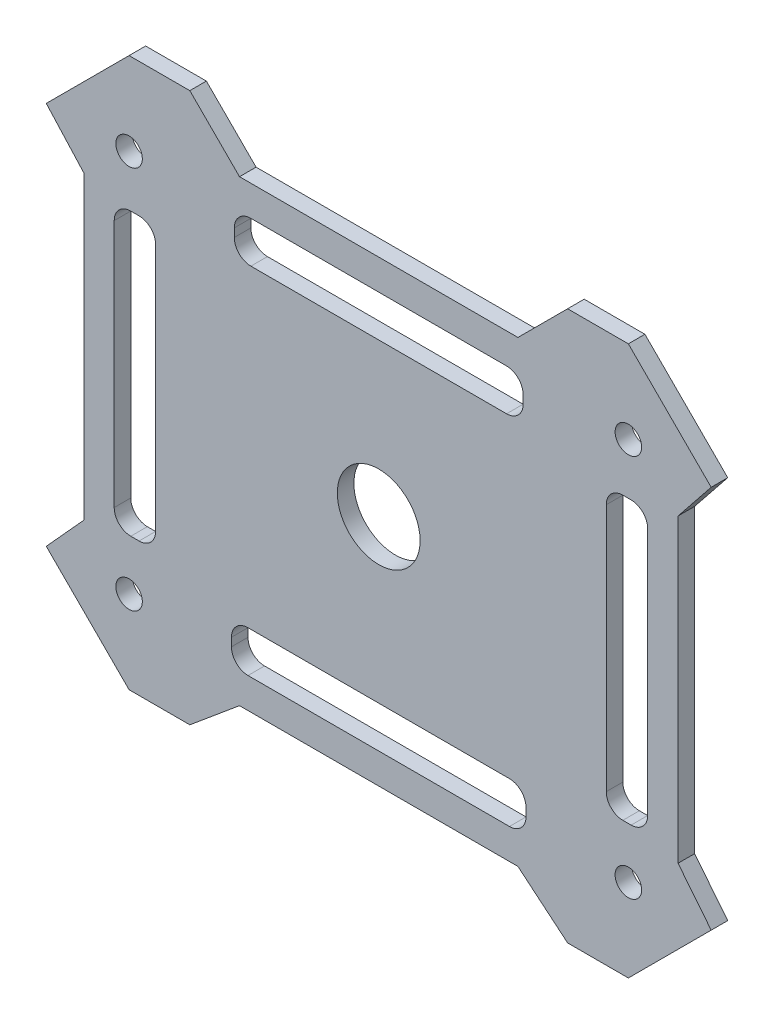
SolidWorks part; units mm, degrees
ref_plane "Front Plane" through (0, 0, 0) normal (0, 0, 1) x (1, 0, 0)
ref_plane "Top Plane" through (0, 0, 0) normal (0, 1, 0) x (1, 0, 0)
ref_plane "Right Plane" through (0, 0, 0) normal (1, 0, 0) x (0, 0, -1)
sketch "Sketch1" plane through (0, 0, 0) normal (0, 0, 1) x (1, 0, 0)
  line L0 (-66.8215, 56.7885) -> (-51.8215, 71.7885)
  line L1 (-31.8215, 62.7885) -> (18.6025, 62.7885)
  line L2 (47.6025, 49.2885) -> (47.6025, -5.1805)
  line L3 (-66.8215, -12.6805) -> (-60.0143, -5.1805)
  line L4 (-40.8215, 71.7885) -> (-31.8215, 62.7885)
  line L5 (-51.8215, 71.7885) -> (-40.8215, 71.7885)
  line L6 (38.6025, 71.7885) -> (53.6025, 56.7885)
  line L7 (-66.8215, -12.6805) -> (-51.8215, -27.6805)
  line L8 (-51.8215, -27.6805) -> (-40.8215, -27.6805)
  line L9 (38.6025, -27.6805) -> (53.6025, -12.6805)
  line L10 (27.6025, -27.6805) -> (38.6025, -27.6805)
  line L11 (27.6025, 71.7885) -> (38.6025, 71.7885)
  line L12 (-60.0143, 49.2885) -> (-66.8215, 56.7885)
  line L14 (18.6025, -20.1805) -> (-31.8215, -20.1805)
  line L15 (47.6025, 49.2885) -> (53.6025, 56.7885)
  line L16 (47.6025, -5.1805) -> (53.6025, -12.6805)
  line L17 (18.6025, 62.7885) -> (27.6025, 71.7885)
  line L18 (-31.8215, -20.1805) -> (-40.8215, -27.6805)
  line L19 (18.6025, -20.1805) -> (27.6025, -27.6805)
  line L20 (-51.5143, 47.554) -> (-50.0143, 47.554)
  line L21 (-54.5143, 44.554) -> (-54.5143, -0.446)
  line L22 (-51.5143, -3.446) -> (-50.0143, -3.446)
  line L23 (-47.0143, 44.554) -> (-47.0143, -0.446)
  line L24 (-29.7649, 57.2885) -> (16.546, 57.2885)
  line L25 (-32.7649, 54.2885) -> (-32.7649, 52.7885)
  line L26 (-29.7649, 49.7885) -> (16.546, 49.7885)
  line L27 (19.546, 54.2885) -> (19.546, 52.7885)
  line L28 (39.1025, 47.554) -> (37.6025, 47.554)
  line L29 (42.1025, 44.554) -> (42.1025, -0.446)
  line L30 (39.1025, -3.446) -> (37.6025, -3.446)
  line L31 (34.6025, 44.554) -> (34.6025, -0.446)
  line L32 (17.068, -14.6805) -> (-30.287, -14.6805)
  line L33 (20.068, -11.6805) -> (20.068, -10.1805)
  line L34 (17.068, -7.1805) -> (-30.287, -7.1805)
  line L35 (-33.287, -11.6805) -> (-33.287, -10.1805)
  line L36 (-60.0143, 49.2885) -> (-60.0143, -5.1805)
  arc A0 (39.1025, -3.446) -> (42.1025, -0.446) centre (39.1025, -0.446) ccw
  arc A1 (34.6025, -0.446) -> (37.6025, -3.446) centre (37.6025, -0.446) ccw
  arc A2 (42.1025, 44.554) -> (39.1025, 47.554) centre (39.1025, 44.554) ccw
  arc A3 (37.6025, 47.554) -> (34.6025, 44.554) centre (37.6025, 44.554) ccw
  arc A4 (16.546, 49.7885) -> (19.546, 52.7885) centre (16.546, 52.7885) ccw
  arc A5 (19.546, 54.2885) -> (16.546, 57.2885) centre (16.546, 54.2885) ccw
  arc A6 (-32.7649, 52.7885) -> (-29.7649, 49.7885) centre (-29.7649, 52.7885) ccw
  arc A7 (-29.7649, 57.2885) -> (-32.7649, 54.2885) centre (-29.7649, 54.2885) ccw
  arc A8 (-47.0143, 44.554) -> (-50.0143, 47.554) centre (-50.0143, 44.554) ccw
  arc A9 (-51.5143, 47.554) -> (-54.5143, 44.554) centre (-51.5143, 44.554) ccw
  arc A10 (-50.0143, -3.446) -> (-47.0143, -0.446) centre (-50.0143, -0.446) ccw
  arc A11 (-54.5143, -0.446) -> (-51.5143, -3.446) centre (-51.5143, -0.446) ccw
  circle A12 centre (-6.6095, 22.054) radius 7.5
  arc A13 (17.068, -14.6805) -> (20.068, -11.6805) centre (17.068, -11.6805) ccw
  arc A14 (20.068, -10.1805) -> (17.068, -7.1805) centre (17.068, -10.1805) ccw
  arc A15 (-30.287, -7.1805) -> (-33.287, -10.1805) centre (-30.287, -10.1805) ccw
  arc A16 (-33.287, -11.6805) -> (-30.287, -14.6805) centre (-30.287, -11.6805) ccw
  circle A17 centre (-51.8215, 56.7885) radius 2.4
  circle A18 centre (38.6025, 56.7885) radius 2.4
  circle A19 centre (38.6025, -12.6805) radius 2.4
  circle A20 centre (-51.8215, -12.6805) radius 2.4
  point P78 (0, 0)
  point P79 (0, 0)
  point P80 (0, 0)
  point P81 (0, 0)
  point P82 (0, 0)
  point P83 (-60.0143, 22.054)
  point P84 (-6.6095, -20.1805)
  point P85 (0, 0)
  point P86 (0, 0)
  point P87 (0, 0)
  point P88 (0, 0)
  point P89 (-46.3215, 71.7885)
  point P90 (-6.6095, 62.7885)
  point P91 (0, 0)
  point P94 (-6.6095, 57.2885)
  point P95 (-6.6095, -7.1805)
  point P96 (-6.6095, 49.7885)
  point P99 (34.6025, 22.054)
  point P100 (47.6025, 22.054)
  point P103 (-47.0143, 22.054)
  dimension "D1" = 15
  dimension "D2" = 15
  dimension "D3" = 15
  dimension "D4" = 15
  dimension "D5" = 15
  dimension "D6" = 15
  dimension "D7" = 15
  dimension "D8" = 15
  dimension "D9" = 9
  dimension "D10" = 90.424
  dimension "D11" = 11
  dimension "D12" = 11
  dimension "D13" = 69.469
  dimension "D14" = 9
  dimension "D15" = 9
  dimension "D16" = 7.5
  dimension "D17" = 7.5
  dimension "D18" = 13
  dimension "D19" = 13
  dimension "D20" = 13
  dimension "D21" = 13
extrude "Boss-Extrude1" add sketch "Sketch1" along normal blind 3
